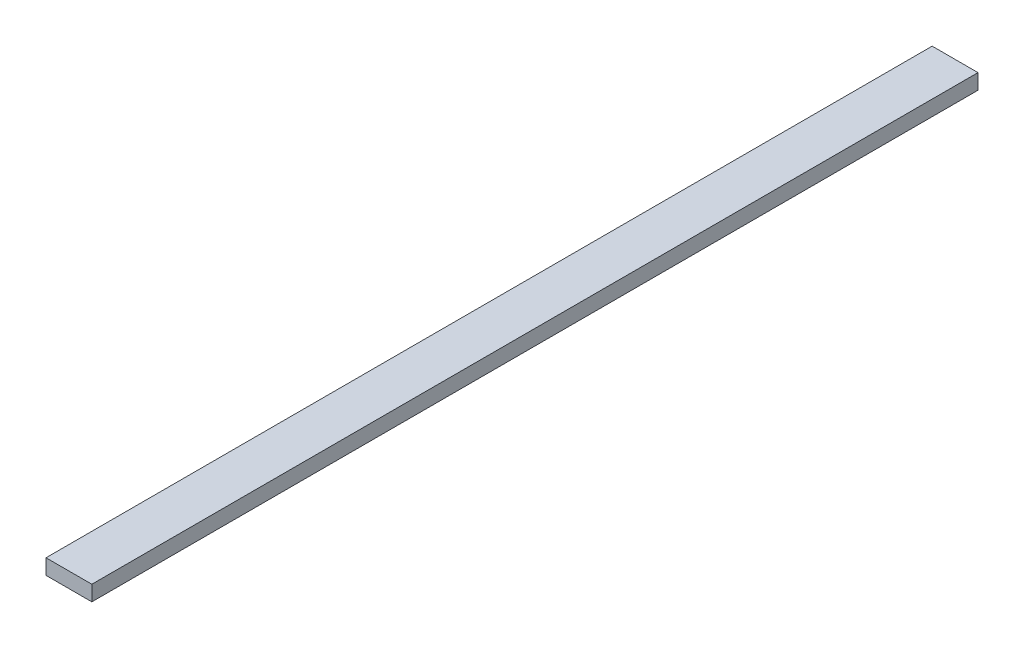
SolidWorks part; units mm, degrees
material "Pine"
ref_plane "Front Plane" through (0, 0, 0) normal (0, 0, 1) x (1, 0, 0)
ref_plane "Top Plane" through (0, 0, 0) normal (0, 1, 0) x (1, 0, 0)
ref_plane "Right Plane" through (0, 0, 0) normal (1, 0, 0) x (0, 0, -1)
sketch "Sketch1" plane through (0, 0, 0) normal (0, 0, 1) x (1, 0, 0)
  line L1 (0, 0) -> (38.1, 0)
  line L2 (0, 0) -> (0, 12.7)
  line L3 (0, 12.7) -> (38.1, 12.7)
  line L4 (38.1, 0) -> (38.1, 12.7)
  dimension "D1" = 38.1
  dimension "D2" = 12.7
extrude "Boss-Extrude1" add sketch "Sketch1" along normal blind 736.6
sketch "Sketch2" plane through (0, 0, 0) normal (0, 0, -1) x (-1, 0, 0)
  line L1 (-38.1, 0) -> (-38.1, 12.7) construction
  line L2 (0, 12.7) -> (0, 0) construction
  line L3 (-19.05, 6.35) -> (-38.1, 6.35) construction
  line L4 (-19.05, 6.35) -> (0, 6.35) construction
  circle A0 centre (-28.575, 6.35) radius 0.8763
  circle A1 centre (-9.525, 6.35) radius 0.8763
  dimension "D1" = 1.7526
sketch "Sketch3" plane through (0, 0, 0) normal (0, -1, 0) x (1, 0, 0)
  line L0 (19.05, 736.6) -> (19.05, 692.15) construction
  line L1 (0, 736.6) -> (38.1, 736.6) construction
  line L2 (19.05, 692.15) -> (19.05, 647.7) construction
  line L3 (38.1, 368.3) -> (0, 368.3) construction
  line L4 (38.1, 736.6) -> (38.1, 0) construction
  line L5 (0, 736.6) -> (0, 0) construction
  line L6 (19.05, 368.3) -> (19.05, 412.75) construction
  line L7 (19.05, 368.3) -> (19.05, 323.85) construction
  circle A0 centre (19.05, 714.375) radius 0.8763
  circle A1 centre (19.05, 669.925) radius 0.8763
  circle A2 centre (19.05, 22.225) radius 0.8763
  circle A3 centre (19.05, 66.675) radius 0.8763
  circle A4 centre (19.05, 346.075) radius 0.8763
  circle A5 centre (19.05, 390.525) radius 0.8763
  dimension "D2" = 1.7526
  dimension "D4" = 1.7526
  dimension "D1" = 88.9
  dimension "D3" = 88.9
equation "\"length\"= 20"
equation "\"length\"= 22"
equation "\"length\"= 36"
equation "\"length\"= 26"
equation "\"length\"= 27"
equation "\"length\"= 28"
equation "\"length\"= 39"
equation "\"length\"= 96"
equation "\"length\"= 30"
equation "\"length\"= 32"
